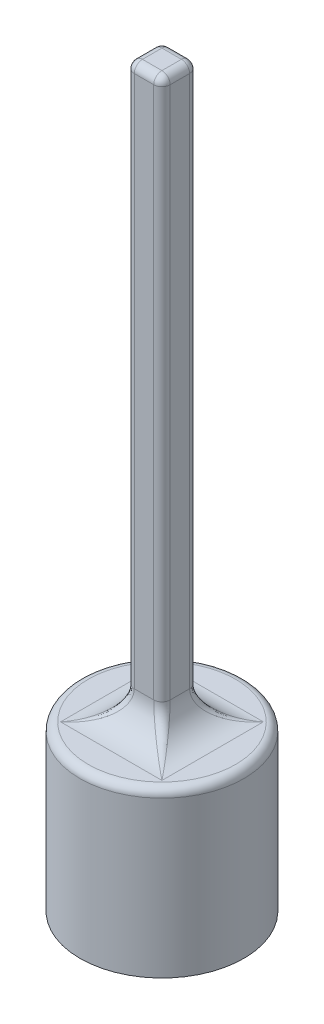
SolidWorks part; units mm, degrees
material "Plain Carbon Steel"
ref_plane "Front Plane" through (0, 0, 0) normal (0, 0, 1) x (1, 0, 0)
ref_plane "Top Plane" through (0, 0, 0) normal (0, 1, 0) x (1, 0, 0)
ref_plane "Right Plane" through (0, 0, 0) normal (1, 0, 0) x (0, 0, -1)
sketch "Sketch1" plane through (0, 0, 0) normal (0, 1, 0) x (0, 0, -1)
  circle A0 centre (0, 0) radius 6.35
  dimension "D1" = 12.7
extrude "Boss-Extrude1" add sketch "Sketch1" along normal blind 12.7 contours A0
sketch "Sketch2" plane through (-12.7, 12.7, 0) normal (0, -1, 0) x (0, 0, -1)
  line L1 (1.3891, 14.0891) -> (-1.3891, 14.0891)
  line L2 (1.3891, 14.0891) -> (1.3891, 11.3109)
  line L3 (1.3891, 11.3109) -> (-1.3891, 11.3109)
  line L4 (-1.3891, 14.0891) -> (-1.3891, 11.3109)
  line L5 (1.3891, 14.0891) -> (-1.3891, 11.3109) construction
  line L6 (1.3891, 11.3109) -> (-1.3891, 14.0891) construction
  point P0 (0, 12.7)
  dimension "D1" = 2.7781
extrude "Boss-Extrude2" add sketch "Sketch2" against normal blind 44.45 contours L1 L4 L3 L2
fillet "Fillet1" radius 2.54 4 edges at (0, 12.7, 1.3891) (-1.3891, 12.7, 0) (0, 12.7, -1.3891) (1.3891, 12.7, 0)
fillet "Fillet2" radius 0.635 13 edges at (2.133, 13.4439, 2.133) (-2.133, 13.4439, 2.133) (2.133, 13.4439, -2.133) (-2.133, 13.4439, -2.133) (1.3891, 36.195, 1.3891) (-1.3891, 36.195, 1.3891) (1.3891, 36.195, -1.3891) (-1.3891, 36.195, -1.3891) (0, 12.7, 6.35) (0, 57.15, -1.3891) (1.3891, 57.15, 0) (0, 57.15, 1.3891) (-1.3891, 57.15, 0)
sketch "Sketch3" plane through (0, 0, 0) normal (0, -1, 0) x (1, 0, 0)
  line L1 (-3.3909, 1.9577) -> (-3.3909, -1.9577)
  line L2 (-3.3909, -1.9577) -> (0, -3.9155)
  line L3 (0, -3.9155) -> (3.3909, -1.9577)
  line L4 (3.3909, -1.9577) -> (3.3909, 1.9577)
  line L5 (3.3909, 1.9577) -> (0, 3.9155)
  line L6 (0, 3.9155) -> (-3.3909, 1.9577)
  circle A0 centre (0, 0) radius 3.3909 construction
  dimension "D1" = 6.7818
extrude "Cut-Extrude1" cut sketch "Sketch3" against normal blind 10.033
fillet "Fillet3" radius 3.175 6 edges at (1.6955, 10.033, 2.9366) (3.3909, 10.033, 0) (1.6954, 10.033, -2.9366) (-1.6955, 10.033, -2.9366) (-3.3909, 10.033, 0) (-1.6955, 10.033, 2.9366)
